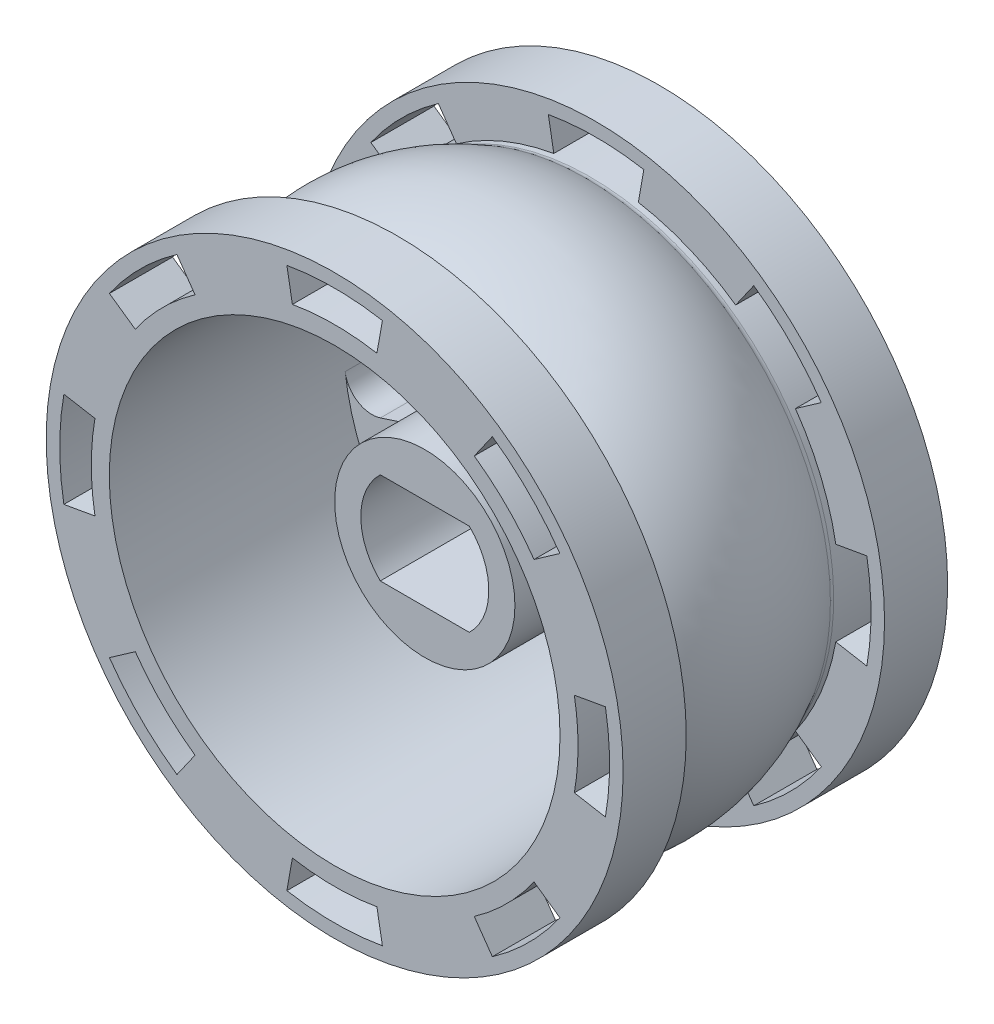
SolidWorks part; units mm, degrees
ref_plane "前视基准面" through (0, 0, 0) normal (0, 0, 1) x (1, 0, 0)
ref_plane "上视基准面" through (0, 0, 0) normal (0, 1, 0) x (1, 0, 0)
ref_plane "右视基准面" through (0, 0, 0) normal (1, 0, 0) x (0, 0, -1)
sketch "草图1" plane through (0, 0, 0) normal (0, 0, 1) x (1, 0, 0)
  circle A0 centre (0, 0) radius 16
  dimension "D1" = 32
extrude "凸台-拉伸1" add sketch "草图1" along normal mid plane 18
sketch "草图2" plane through (0, 0, 9) normal (0, 0, 1) x (1, 0, 0)
  circle A0 centre (0, 0) radius 12.5
  dimension "D1" = 25
extrude "切除-拉伸1" cut sketch "草图2" against normal blind 13
sketch "草图3" plane through (0, 0, -4) normal (0, 0, 1) x (1, 0, 0)
  line L0 (-3.25, -3.7997) -> (-8.8425, -8.8352)
  line L1 (0, -5) -> (0, -13.2102) construction
  line L2 (3.25, -3.7997) -> (8.8425, -8.8352)
  circle A0 centre (0, 0) radius 5
  circle A1 centre (0, 0) radius 12.5 construction
  circle A2 centre (0, 0) radius 12.5
  circle M3 centre (0, 0) radius 12.5
  dimension "D1" = 10
  dimension "D2" = 96
  dimension "D3" = 6.5
extrude "切除-拉伸2" cut sketch "草图3" against normal blind 10 contours A0 L1 A2 L2 | L1 A0 L0 M3
pattern_circular "阵列(圆周)1" count 3 over 360 about axis through (0, 0, 0) along (0, 0, 1) of "切除-拉伸2"
sketch "草图4" plane through (0, 0, -4) normal (0, 0, 1) x (1, 0, 0)
  circle A0 centre (0, 0) radius 5
  dimension "D1" = 10
extrude "凸台-拉伸2" add sketch "草图4" along normal blind 8
sketch "草图5" plane through (0, 0, 4) normal (0, 0, 1) x (1, 0, 0)
  line L1 (-5.637, 2.55) -> (5.637, 2.55)
  line L2 (-5.637, 2.55) -> (-5.637, -2.55)
  line L3 (-5.637, -2.55) -> (5.637, -2.55)
  line L4 (5.637, 2.55) -> (5.637, -2.55)
  line L5 (-5.637, 2.55) -> (5.637, -2.55) construction
  line L6 (-5.637, -2.55) -> (5.637, 2.55) construction
  circle A0 centre (0, 0) radius 3.55
  dimension "D1" = 7.1
  dimension "D2" = 5.1
extrude "切除-拉伸3" cut sketch "草图5" against normal blind 16 contours L1 A0 L3
sketch "草图6" plane through (0, 0, -9) normal (0, 0, -1) x (-1, 0, 0)
  circle A0 centre (0, 0) radius 10 construction
  circle A1 centre (0, 10) radius 1.275
  dimension "D1" = 20
  dimension "D2" = 2.55
extrude "切除-拉伸4" cut sketch "草图6" against normal blind 10
pattern_circular "阵列(圆周)2" count 3 over 360 about axis through (0, 0, 0) along (0, 0, 1) of "切除-拉伸4"
sketch "草图7" plane through (0, 0, 0) normal (0, 0, 1) x (1, 0, 0)
  circle A0 centre (0, 0) radius 13.5
  circle A1 centre (0, 0) radius 20
  dimension "D1" = 27
  dimension "D2" = 40
extrude "切除-拉伸5" cut sketch "草图7" against normal mid plane 11
sketch "草图8" plane through (0, 0, -5.5) normal (0, 0, 1) x (1, 0, 0)
  line L0 (0, 0) -> (-2.6481, 15.0183)
  line L1 (0, 0) -> (0, 16) construction
  line L2 (0, 0) -> (2.6481, 15.0183)
  circle A0 centre (0, 0) radius 15.25
  circle A3 centre (0, 0) radius 13.5
  circle A4 centre (0, 0) radius 16 construction
  circle M3 centre (0, 0) radius 13.5
  dimension "D1" = 30.5
  dimension "D2" = 27
  dimension "D3" = 20
extrude "切除-拉伸6" cut sketch "草图8" against normal blind 5 contours L1 A0 L0 M3 | L1 A3 L2 A0
mirror "镜向1" about plane through (0, 0, 0) normal (0, 0, 1) of "切除-拉伸6"
pattern_circular "阵列(圆周)3" count 8 over 360 about axis through (0, 0, 0) along (0, 0, 1) of "镜向1", "切除-拉伸6"
fillet "圆角1" radius 1.5 12 edges at (-3.25, -3.7997, -6.5) (3.25, -3.7997, -6.5) (8.8425, -8.8352, -6.5) (-8.8425, -8.8352, -6.5) (4.9156, -0.9147, -6.5) (1.6656, 4.7144, -6.5) (3.2302, 12.0754, -6.5) (12.0727, -3.2402, -6.5) (-1.6656, 4.7144, -6.5) (-4.9156, -0.9147, -6.5) (-12.0727, -3.2402, -6.5) (-3.2302, 12.0754, -6.5)
sketch "草图9" plane through (0, 0, 0) normal (0, 1, 0) x (1, 0, 0)
  line L0 (0, 0) -> (-4.8659, 0) construction
  line L1 (-13.3, -5.3728) -> (-13.3, 5.3728)
  line L2 (-13.5, 9) -> (-13.5, -9) construction
  line L3 (0, 0) -> (0, 10.7028) construction
  arc A0 (-13.3, 5.3728) -> (-13.3, -5.3728) centre (-4.8659, 0) ccw
  point P3 (-30.5683, 6.4542)
  dimension "D1" = 20
  dimension "D3" = 0.2
revolve "旋转1" add sketch "草图9" angle 360 about L3
fillet "圆角2" radius 0.5 1 edges at (13.5, 0, -5.0451)
equation "\"1。5\"=2"
